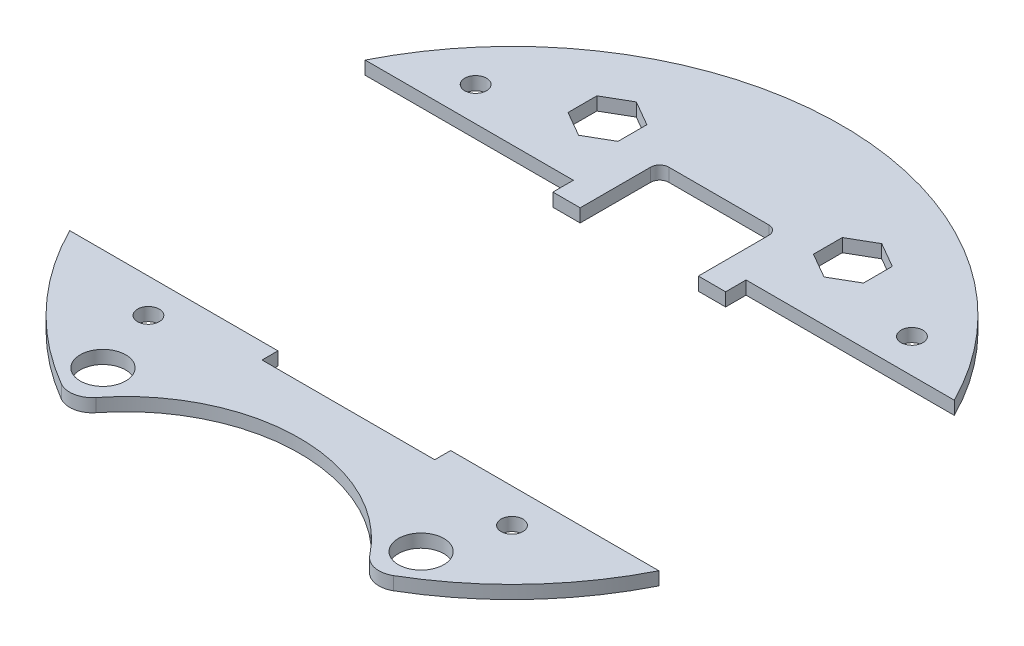
SolidWorks part; units mm, degrees
material "Acrylic (Medium-high impact)"
ref_plane "Front Plane" through (0, 0, 0) normal (0, 0, 1) x (1, 0, 0)
ref_plane "Top Plane" through (0, 0, 0) normal (0, 1, 0) x (1, 0, 0)
ref_plane "Right Plane" through (0, 0, 0) normal (1, 0, 0) x (0, 0, -1)
sketch "Sketch1" plane through (0, 0, 0) normal (0, 1, 0) x (1, 0, 0)
  line L0 (0, -85) -> (-32.4891, -64.8129) construction
  line L1 (0, -85) -> (0, 0) construction
  arc A0 (36.5434, -62.6165) -> (-36.5434, -62.6165) centre (0, 0) ccw
  arc A1 (30.0898, -61.3851) -> (-30.0898, -61.3851) centre (0, -85) ccw
  arc A2 (-30.0898, -61.3851) -> (-36.5434, -62.6165) centre (-34.0231, -58.2982) cw
  arc A3 (36.5434, -62.6165) -> (30.0898, -61.3851) centre (34.0231, -58.2982) cw
  dimension "D1" = 145
  dimension "D2" = 76.5
  dimension "D4" = 5
  dimension "D3" = 85
extrude "Boss-Extrude1" add sketch "Sketch1" along normal blind 2.9
sketch "solenoid placement" plane through (0, 2.9, 0) normal (0, 1, 0) x (1, 0, 0)
  line L4 (-19, -36) -> (19, -36)
  line L5 (-19, 28) -> (-19, -36)
  line L6 (19, 28) -> (-19, 28)
  line L7 (19, -36) -> (19, 28)
  line L8 (-19, -36) -> (19, -36)
  line L9 (-19, 28) -> (-19, -36)
  line L10 (19, 28) -> (-19, 28)
  line L11 (19, -36) -> (19, 28)
  dimension "D1" = 0
extrude "Cut-Extrude1" cut sketch "solenoid placement" against normal through all
sketch "Sketch4" plane through (0, 2.9, 0) normal (0, 1, 0) x (1, 0, 0)
  line L8 (13, 28) -> (13, 43.5)
  line L9 (-13, 28) -> (13, 28)
  line L10 (-13, 43.5) -> (-13, 28)
  line L11 (11, 45.5) -> (-11, 45.5)
  line L28 (13, 28) -> (13, 43.5)
  line L29 (-13, 28) -> (13, 28)
  line L30 (-13, 43.5) -> (-13, 28)
  line L31 (11, 45.5) -> (-11, 45.5)
  arc A4 (-11, 45.5) -> (-13, 43.5) centre (-11, 43.5) ccw
  arc A5 (13, 43.5) -> (11, 45.5) centre (11, 43.5) ccw
  arc A14 (-11, 45.5) -> (-13, 43.5) centre (-11, 43.5) ccw
  arc A15 (13, 43.5) -> (11, 45.5) centre (11, 43.5) ccw
  dimension "D1" = 0
extrude "Cut-Extrude4" cut sketch "Sketch4" against normal through all
sketch "Sketch5" plane through (0, 2.9, 0) normal (0, 1, 0) x (1, 0, 0)
  line L12 (-21.5, 51.1754) -> (-27, 54.3509)
  line L13 (-27, 54.3509) -> (-32.5, 51.1754)
  line L14 (-32.5, 51.1754) -> (-32.5, 44.8246)
  line L15 (-32.5, 44.8246) -> (-27, 41.6491)
  line L16 (-27, 41.6491) -> (-21.5, 44.8246)
  line L17 (-21.5, 44.8246) -> (-21.5, 51.1754)
  line L18 (-21.5, 51.1754) -> (-27, 54.3509)
  line L19 (-27, 54.3509) -> (-32.5, 51.1754)
  line L20 (-32.5, 51.1754) -> (-32.5, 44.8246)
  line L21 (-32.5, 44.8246) -> (-27, 41.6491)
  line L22 (-27, 41.6491) -> (-21.5, 44.8246)
  line L23 (-21.5, 44.8246) -> (-21.5, 51.1754)
  line L24 (21.5, 51.1754) -> (21.5, 44.8246)
  line L25 (21.5, 44.8246) -> (27, 41.6491)
  line L26 (27, 41.6491) -> (32.5, 44.8246)
  line L27 (32.5, 44.8246) -> (32.5, 51.1754)
  line L28 (32.5, 51.1754) -> (27, 54.3509)
  line L29 (27, 54.3509) -> (21.5, 51.1754)
  line L42 (21.5, 51.1754) -> (21.5, 44.8246)
  line L43 (21.5, 44.8246) -> (27, 41.6491)
  line L44 (27, 41.6491) -> (32.5, 44.8246)
  line L45 (32.5, 44.8246) -> (32.5, 51.1754)
  line L46 (32.5, 51.1754) -> (27, 54.3509)
  line L47 (27, 54.3509) -> (21.5, 51.1754)
  dimension "D1" = 0
  dimension "D2" = 0
extrude "Cut-Extrude5" cut sketch "Sketch5" against normal through all
sketch "Sketch6" plane through (0, 2.9, 0) normal (0, 1, 0) x (1, 0, 0)
  circle A1 centre (40, -40) radius 2.4
  circle A2 centre (40, -40) radius 2.4
  circle A3 centre (-40, -40) radius 2.4
  circle A4 centre (-40, -40) radius 2.4
  circle A5 centre (48, 40) radius 2.4
  circle A6 centre (48, 40) radius 2.4
  circle A7 centre (-48, 40) radius 2.4
  circle A8 centre (-48, 40) radius 2.4
  dimension "D1" = 0
  dimension "D2" = 0
  dimension "D3" = 0
  dimension "D4" = 0
extrude "Cut-Extrude6" cut sketch "Sketch6" against normal through all
sketch "Sketch3" plane through (0, 2.9, 0) normal (0, 1, 0) x (1, 0, 0)
  line L0 (-19, 28) -> (-19, 32.5)
  line L1 (72.5, -32.5) -> (-72.5, -32.5)
  line L2 (72.5, -32.5) -> (72.5, 32.5)
  line L3 (72.5, 32.5) -> (19, 32.5)
  line L4 (-72.5, -32.5) -> (-72.5, 32.5)
  line L5 (72.5, -32.5) -> (-72.5, 32.5) construction
  line L6 (72.5, 32.5) -> (-72.5, -32.5) construction
  line L7 (-19, 28) -> (19, 28)
  line L8 (19, 28) -> (19, 32.5)
  line L9 (-19, 32.5) -> (-72.5, 32.5)
  line L10 (-19, 28) -> (-19, -36) construction
  line L11 (-13, 28) -> (-19, 28) construction
  arc A0 (36.5434, -62.6165) -> (-36.5434, -62.6165) centre (0, 0) ccw construction
  point P0 (0, 0)
  dimension "D1" = 65
extrude "Cut-Extrude3" cut sketch "Sketch3" against normal through all
sketch "Sketch7" plane through (0, 2.9, 0) normal (0, 1, 0) x (1, 0, 0)
  circle A1 centre (35, -55) radius 5
  circle A2 centre (35, -55) radius 5
  circle A3 centre (-35, -55) radius 5
  circle A4 centre (-35, -55) radius 5
  dimension "D1" = 0
  dimension "D2" = 0
extrude "Cut-Extrude7" cut sketch "Sketch7" against normal through all
equation "\"smallPulleyTeeth\"= 15"
equation "\"largePulleyTeeth\"= 30"
equation "\"eighthThick\"= 2.9mm"
equation "\"sixteenthThick\" = 1.7mm"
equation "\"quarterThick\"=6.0mm"
equation "\"OD\" = 145mm"
equation "\"puckAngle\" = 60.5deg"
equation "\"D1@Sketch1\"=\"OD\""
equation "\"puckDiam\" = 76.5mm"
equation "\"D2@Sketch1\"=\"puckDiam\""
equation "\"D1@Boss-Extrude1\"=\"eighthThick\""
equation "\"axlePress\" = 5.9mm"
equation "\"press\" = 0.2mm"
equation "\"wheelClear\" = 0.3mm"
equation "\"10-32clear\" = 4.8mm"
equation "\"6-32clear\" = 3.3mm"
equation "\"8-32clear\" = 4.0mm"
equation "\"wheelHeight\" = 22mm"
equation "\"wheelWell\" = 65mm"
equation "\"D1@Sketch3\"=\"wheelWell\""
equation "\"puckDist\" = 85mm"
equation "\"scoopFillet\" = 5mm"
equation "\"4-40clear\" = 3.0mm"
equation "\"D3@Sketch1\"=\"puckDist\""
equation "\"D4@Sketch1\"=\"scoopFillet\""
